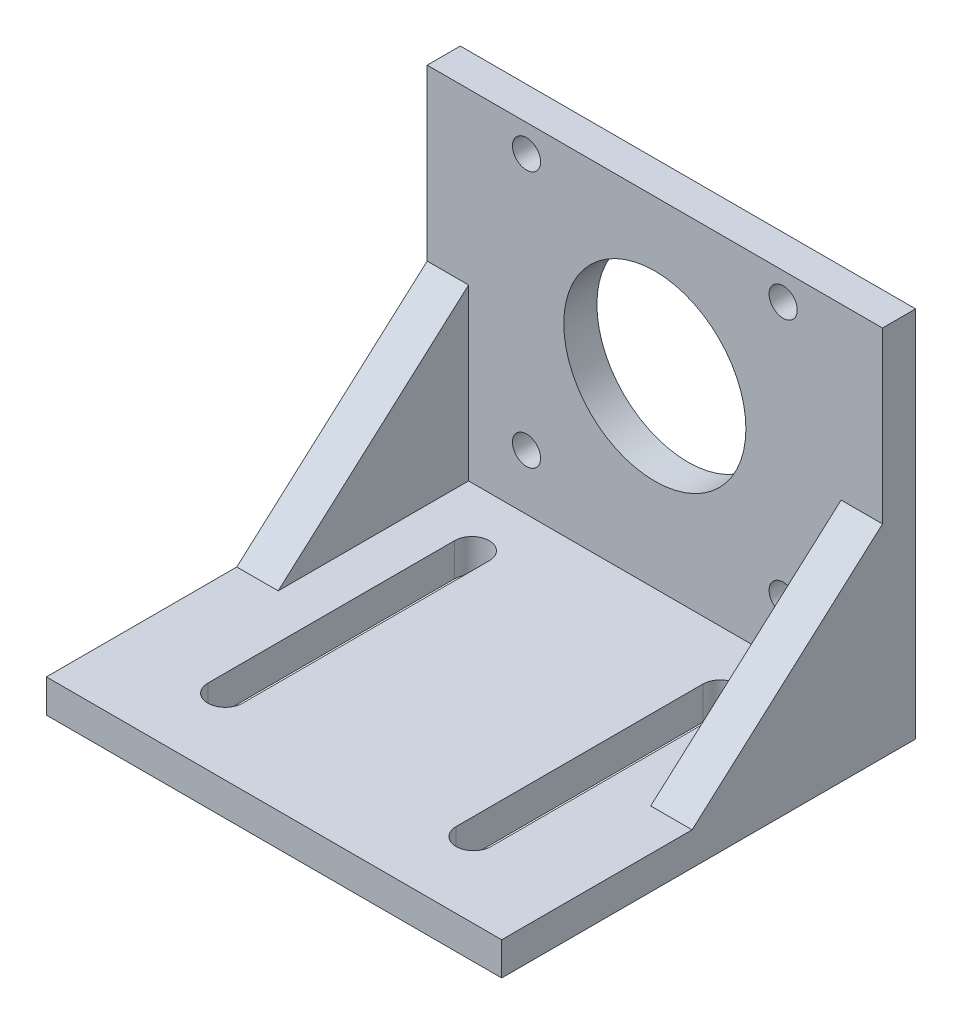
SolidWorks part; units mm, degrees
ref_plane "前视基准面" through (0, 0, 0) normal (0, 0, 1) x (1, 0, 0)
ref_plane "上视基准面" through (0, 0, 0) normal (0, 1, 0) x (1, 0, 0)
ref_plane "右视基准面" through (0, 0, 0) normal (1, 0, 0) x (0, 0, -1)
sketch "Sketch1" plane through (0, 0, 0) normal (1, 0, 0) x (0, 0, -1)
  line L0 (0, 0) -> (50, 0)
  line L1 (50, 0) -> (50, 45)
  line L2 (50, 45) -> (46, 45)
  line L3 (46, 45) -> (46, 4)
  line L4 (46, 4) -> (0, 4)
  line L5 (0, 4) -> (0, 0)
  dimension "D1" = 50
  dimension "D2" = 4
  dimension "D3" = 45
extrude "Boss-Extrude1" add sketch "Sketch1" along normal mid plane 55
sketch "Sketch2" plane through (0, 4, 0) normal (0, 1, 0) x (1, 0, 0)
  line B0 (-12.9, 9.1) -> (-12.9, 38.9)
  line B1 (-17.1, 38.9) -> (-17.1, 9.1)
  line B2 (12.9, 38.9) -> (12.9, 9.1)
  line B3 (17.1, 9.1) -> (17.1, 38.9)
  arc B4 (-12.9, 38.9) -> (-17.1, 38.9) centre (-15, 38.9) ccw
  arc B5 (-17.1, 9.1) -> (-15, 7) centre (-15, 9.1) ccw
  arc B6 (-15, 7) -> (-12.9, 9.1) centre (-15, 9.1) ccw
  arc B7 (17.1, 38.9) -> (12.9, 38.9) centre (15, 38.9) ccw
  arc B8 (12.9, 9.1) -> (15, 7) centre (15, 9.1) ccw
  arc B9 (15, 7) -> (17.1, 9.1) centre (15, 9.1) ccw
sketch_block_instance "Block1-1"
sketch_block "Block1"
extrude "Cut-Extrude1" cut sketch "Sketch2" against normal up to next
sketch "Sketch3" plane through (0, 0, -46) normal (0, 0, 1) x (1, 0, 0)
  arc B0 (11, 26.2168) -> (-11, 26.2168) centre (0, 26.2168) ccw
  arc B1 (-11, 26.2168) -> (11, 26.2168) centre (0, 26.2168) ccw
  arc B2 (-17.2, 10.7168) -> (-13.8, 10.7168) centre (-15.5, 10.7168) ccw
  arc B3 (-13.8, 10.7168) -> (-17.2, 10.7168) centre (-15.5, 10.7168) ccw
  arc B4 (-17.2, 41.7168) -> (-13.8, 41.7168) centre (-15.5, 41.7168) ccw
  arc B5 (-13.8, 41.7168) -> (-17.2, 41.7168) centre (-15.5, 41.7168) ccw
  arc B6 (13.8, 41.7168) -> (17.2, 41.7168) centre (15.5, 41.7168) ccw
  arc B7 (17.2, 41.7168) -> (13.8, 41.7168) centre (15.5, 41.7168) ccw
  arc B8 (17.2, 10.7168) -> (13.8, 10.7168) centre (15.5, 10.7168) ccw
  arc B9 (13.8, 10.7168) -> (17.2, 10.7168) centre (15.5, 10.7168) ccw
sketch_block_instance "Block2-1"
sketch_block "Block2"
extrude "Cut-Extrude2" cut sketch "Sketch3" against normal up to next
sketch "Sketch5" plane through (27.5, 0, 0) normal (1, 0, 0) x (0, 0, -1)
  line L0 (46, 24.5) -> (23, 4)
  line L1 (46, 45) -> (46, 4) construction
  line L2 (46, 4) -> (0, 4) construction
  line L3 (23, 4) -> (46, 4)
  line L4 (46, 4) -> (46, 24.5)
extrude "Boss-Extrude2" add sketch "Sketch5" against normal blind 5
extrude "Boss-Extrude3" add sketch "Sketch5<2>" along normal blind 5 from surface starting at face at (-27.5, 16.3333, -32)
sketch "Sketch5<2>" plane through (27.5, 0, 0) normal (1, 0, 0) x (0, 0, -1) same geometry as "Sketch5"
